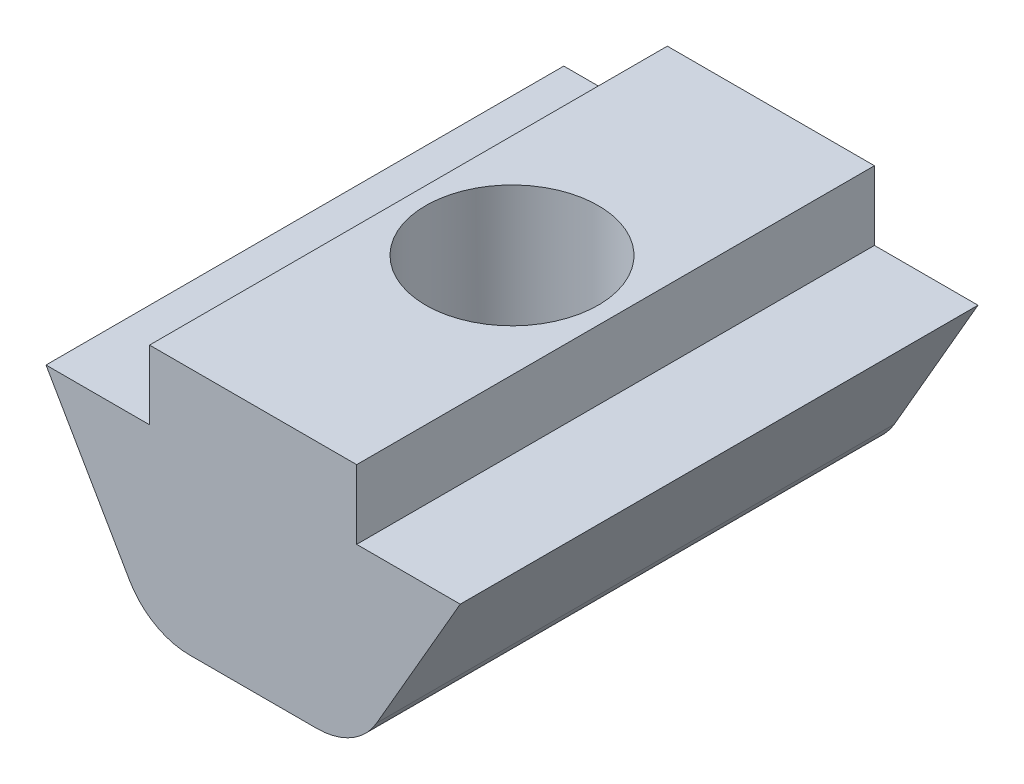
SolidWorks part; units mm, degrees
material "AISI 321 Annealed Stainless Steel (SS)"
ref_plane "Front Plane" through (0, 0, 0) normal (0, 0, 1) x (1, 0, 0)
ref_plane "Top Plane" through (0, 0, 0) normal (0, 1, 0) x (1, 0, 0)
ref_plane "Right Plane" through (0, 0, 0) normal (1, 0, 0) x (0, 0, -1)
sketch "Sketch2" plane through (0, 0, 0) normal (0, 0, 1) x (1, 0, 0)
  line L0 (-3, 0) -> (3, 0)
  line L1 (-3, 0) -> (-6, 5.1962)
  line L2 (0, 5) -> (0, 0) construction
  line L3 (3, 0) -> (6, 5.1962)
  line L4 (-6, 5.1962) -> (6, 5.1962)
  line L5 (3, 5.1962) -> (3, 7.1962)
  line L6 (0, 5.1962) -> (-3, 5.1962)
  line L7 (0, 5.1962) -> (0, 5)
  line L8 (3, 7.1962) -> (-3, 7.1962)
  line L9 (-3, 5.1962) -> (-3, 7.1962)
  point P4 (0, 0)
  point P11 (0, 7.1962)
  dimension "D1" = 6
  dimension "D2" = 5
  dimension "D3" = 120
  dimension "D4" = 6
  dimension "D5" = 6
  dimension "D6" = 2
extrude "Boss-Extrude1" add sketch "Sketch2" along normal mid plane 15 contours L2 L4 L1 L0 | L4 L2 L0 L3 | L9 L4 L5 L8 region at (0, 2.8868, 0) region at (0, 6.1962, 0)
hole_wizard "M6 Tapped Hole1" positions "Sketch3" profile "Sketch4" tap size "M6" standard "ISO" end condition through all
sketch "Sketch3" plane through (0, 7.1962, 0) normal (0, 1, 0) x (1, 0, 0)
  point P0 (0, 0)
sketch "Sketch4" plane through (0, 7.1962, 0) normal (1, 0, 0) x (0, 0, 1)
  line L0 (0, 0) -> (0, 7.1962)
  line L1 (0, 7.1962) -> (2.5, 7.1962)
  line L2 (2.5, 7.1962) -> (2.5, 0)
  line L5 (2.5, 0) -> (0, 0)
  line L11 (0, -6.35) -> (0, 107.95) construction
  dimension "Thru Tap Drill Dia." = 5
  dimension "Thru Tap Drill Depth" = 7.1962
cosmetic thread "Hole Thread1" parameters "D2"=6
fillet "Fillet1" radius 2 2 edges at (3, 0, 0) (-3, 0, 0)
